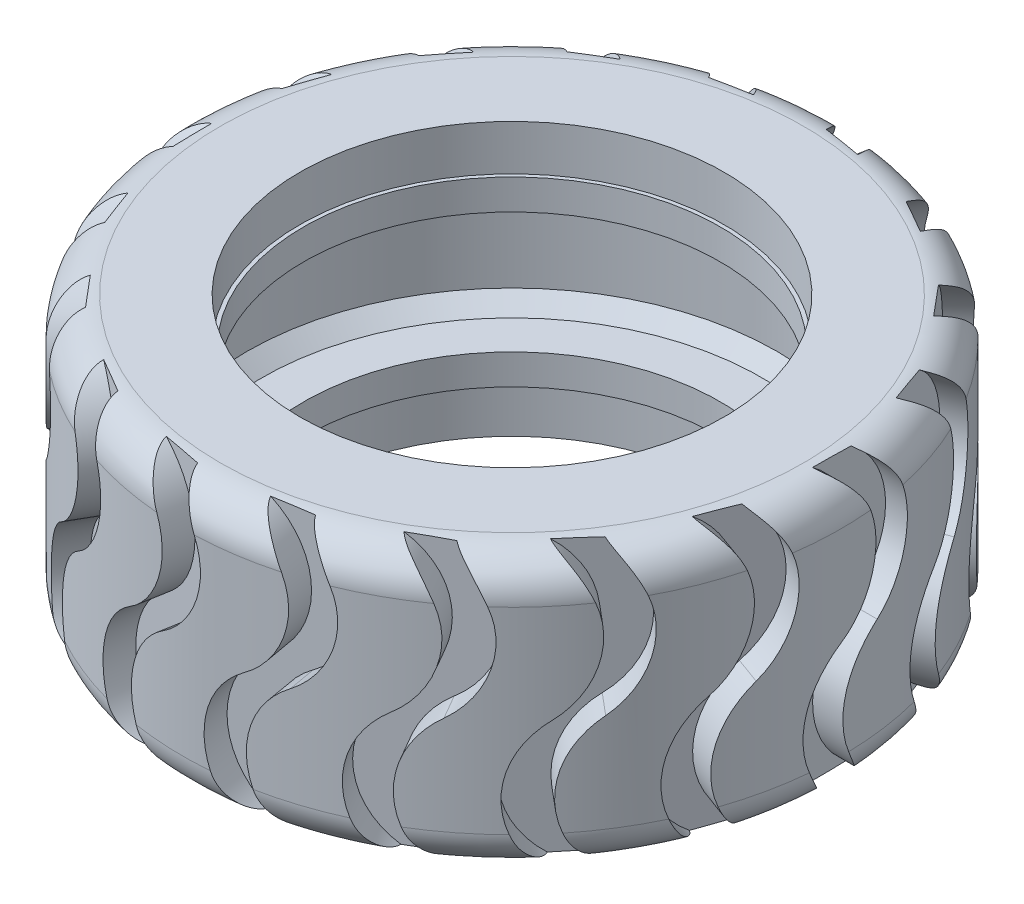
SolidWorks part; units mm, degrees
material "POLYURETHANE (11671)"
ref_plane "Front Plane" through (0, 0, 0) normal (0, 0, 1) x (1, 0, 0)
ref_plane "Top Plane" through (0, 0, 0) normal (0, 1, 0) x (1, 0, 0)
ref_plane "Right Plane" through (0, 0, 0) normal (1, 0, 0) x (0, 0, -1)
ref_axis "Axis1" through (0, 0.5114, 0) along (0, -1, 0)
sketch "Sketch1" plane through (0, 0, 0) normal (1, 0, 0) x (0, 0, -1)
  line L0 (0, -29.8193) -> (0, 37.7711) construction
  line L2 (13.75, -0.3886) -> (21.75, -0.3886)
  line L3 (13.75, -0.3886) -> (13.75, -18.3886)
  line L4 (13.75, -18.3886) -> (21.75, -18.3886)
  line L5 (21.75, -0.3886) -> (21.75, -18.3886)
  line L6 (13.75, -0.3886) -> (21.75, -18.3886) construction
  line L7 (13.75, -18.3886) -> (21.75, -0.3886) construction
  point P3 (17.75, -9.3886)
  dimension "D1" = 27.5
  dimension "D2" = 18
  dimension "D3" = 8
revolve "Revolve1" add sketch "Sketch1" angle 360 about L0
sketch "Sketch2" plane through (0, 0, 0) normal (1, 0, 0) x (0, 0, -1)
  line L0 (0, -0.3886) -> (0, -18.3886) construction
  line L1 (21.75, -0.3886) -> (-21.75, -0.3886) construction
  line L2 (-21.75, -18.3886) -> (21.75, -18.3886) construction
  line L3 (0, -9.3886) -> (21.75, -9.3886) construction
  line L4 (21.75, -18.3886) -> (21.75, -0.3886) construction
  line L5 (14, -0.3886) -> (14, -3.3886)
  line L6 (14, -3.3886) -> (13.75, -3.3886)
  line L7 (13.75, -18.3886) -> (13.75, -0.3886) construction
  line L8 (13.75, -3.3886) -> (13.75, -5.3886)
  line L9 (13.75, -5.3886) -> (16.5, -5.3886)
  line L10 (16.5, -5.3886) -> (17.5, -6.3886)
  line L11 (17.5, -6.3886) -> (17.5, -12.3886)
  line L15 (16.5, -13.3886) -> (17.5, -12.3886)
  line L16 (13.75, -13.3886) -> (16.5, -13.3886)
  line L17 (13.75, -15.3886) -> (13.75, -13.3886)
  line L18 (14, -15.3886) -> (13.75, -15.3886)
  line L19 (14, -18.3886) -> (14, -15.3886)
  line L20 (14, -0.3886) -> (10.75, -0.3886)
  line L21 (10.75, -0.3886) -> (10.75, -18.3886)
  line L22 (-13.75, -18.3886) -> (13.75, -18.3886) construction
  line L23 (10.75, -18.3886) -> (14, -18.3886)
  point P23 (17.5, -9.3886)
  dimension "D1" = 7.75
  dimension "D2" = 3
  dimension "D3" = 2
  dimension "D4" = 3.75
  dimension "D5" = 45
  dimension "D6" = 3
  dimension "D7" = 3
revolve "Cut-Revolve1" cut sketch "Sketch2" angle 360 about L0
fillet "Fillet1" radius 2.5 2 edges at (0, -18.3886, -21.75) (0, -0.3886, -21.75)
ref_plane "Plane-tread" through (21.75, 0, 0) normal (1, 0, 0) x (0, 0, -1)
sketch "Sketch3" plane through (21.75, 0, 0) normal (1, 0, 0) x (0, 0, -1)
  line L0 (0, -0.3886) -> (0, -18.3886) construction
  line L1 (21.75, -0.3886) -> (-21.75, -0.3886) construction
  line L2 (-21.75, -9.3886) -> (21.75, -9.3886) construction
  line L3 (-21.75, -2.8886) -> (-21.75, -15.8886) construction
  line L4 (21.75, -15.8886) -> (21.75, -2.8886) construction
  line L5 (0, -0.3886) -> (2.5, -0.3886)
  line L6 (0, -18.3886) -> (2.5, -18.3886)
  arc A0 (0, -0.3886) -> (0, -9.3886) centre (-3, -4.8886) cw
  arc A1 (2.5, -0.3886) -> (2.5, -9.3886) centre (-0.5, -4.8886) cw
  arc A2 (0, -18.3886) -> (0, -9.3886) centre (3, -13.8886) cw
  arc A3 (2.5, -18.3886) -> (2.5, -9.3886) centre (5.5, -13.8886) cw
  dimension "D1" = 3
  dimension "D2" = 3
  dimension "D3" = 2.5
  dimension "D4" = 2.5
  dimension "D5" = 2.5
  dimension "D6" = 2.5
extrude "Tread-cut" cut sketch "Sketch3" against normal blind 2
pattern_circular "Treads" count 18 over 360 about axis through (0, 0.5114, 0) along (0, -1, 0) of "Tread-cut"
ref_plane "Tire-mount" through (0, -9.3886, 0) normal (0, 1, 0) x (1, 0, 0)
